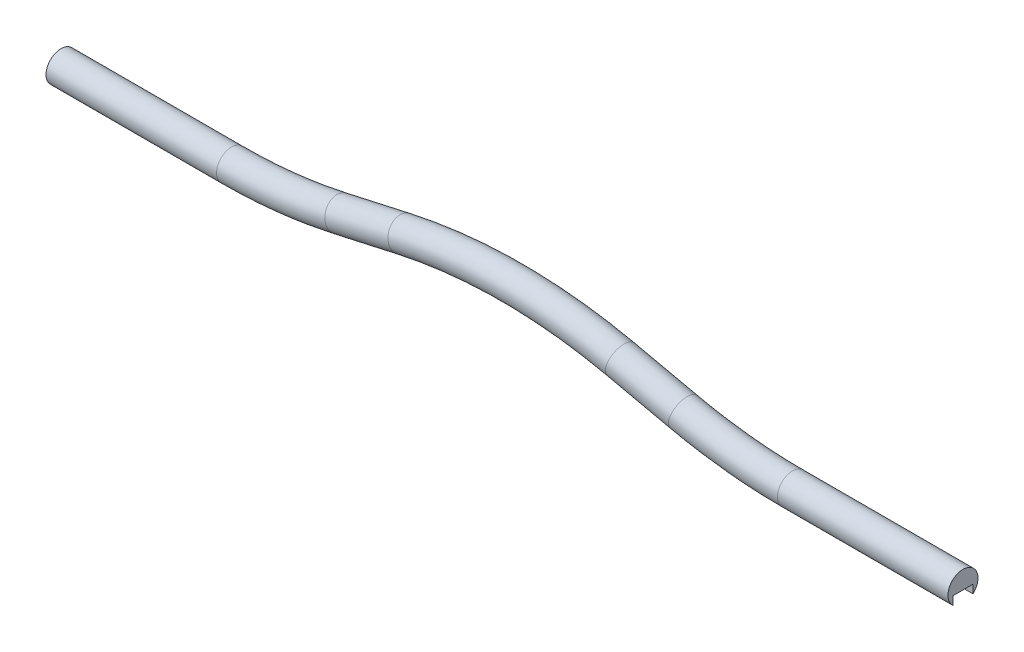
SolidWorks part; units mm, degrees
ref_plane "Front Plane" through (0, 0, 0) normal (0, 0, 1) x (1, 0, 0)
ref_plane "Top Plane" through (0, 0, 0) normal (0, 1, 0) x (1, 0, 0)
ref_plane "Right Plane" through (0, 0, 0) normal (1, 0, 0) x (0, 0, -1)
sketch "Sketch1" plane through (0, 0, 0) normal (0, 0, 1) x (1, 0, 0)
  line L0 (-450, 0) -> (-279.8861, 0)
  line L1 (-171.4209, 11.9065) -> (-108.4652, 25.8966)
  line L3 (171.4209, 11.9065) -> (108.4652, 25.8966)
  line L4 (450, 0) -> (279.8861, 0)
  arc A0 (171.4209, 11.9065) -> (279.8861, 0) centre (279.8861, 500) ccw
  arc A1 (108.4652, 25.8966) -> (-108.4652, 25.8966) centre (0, -462.1969) ccw
  arc A2 (-279.8861, 0) -> (-171.4209, 11.9065) centre (-279.8861, 500) ccw
  point P3 (0, 0)
  point P4 (-7.3876, 50)
  point P5 (-223.0259, 0)
  point P6 (-225, 2.145)
  point P7 (-450, 0)
  point P17 (-225, 0)
  dimension "D1" = 225
  dimension "D3" = 500
  dimension "D2" = 450
sweep "Sweep1" add path "Sketch1" circular profile diameter 30 parameters "D3"=30
sketch "Sketch26" plane through (-450, 0, 0) normal (-1, 0, 0) x (0, 0, 1)
  line L1 (-10, -27.1791) -> (10, -27.1791)
  line L2 (-10, -27.1791) -> (-10, -2.8209)
  line L3 (-10, -2.8209) -> (10, -2.8209)
  line L4 (10, -27.1791) -> (10, -2.8209)
  line L5 (-10, -27.1791) -> (10, -2.8209) construction
  line L6 (-10, -2.8209) -> (10, -27.1791) construction
  circle A0 centre (0, 0) radius 15 construction
  point P0 (0, -15)
extrude "Cut-Extrude2" cut sketch "Sketch26" against normal blind 225
extrude "Cut-Extrude3" cut sketch "Sketch26<2>" along normal blind 225 from surface starting at face at (450, 0, 15)
sketch "Sketch26<2>" plane through (-450, 0, 0) normal (-1, 0, 0) x (0, 0, 1) same geometry as "Sketch26"
